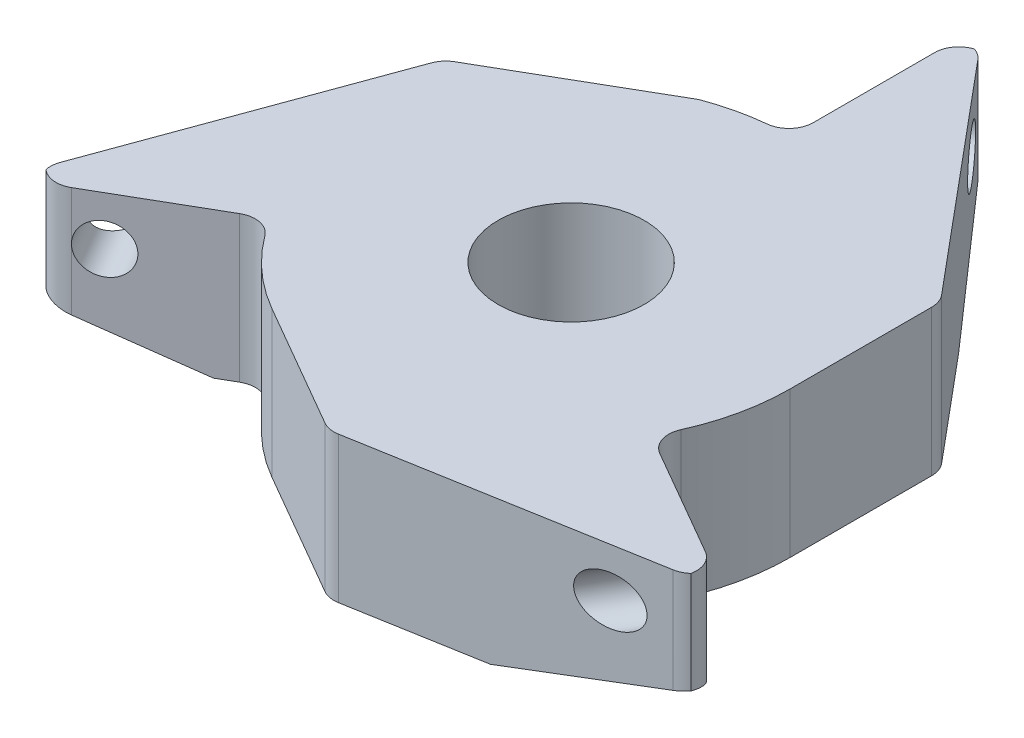
SolidWorks part; units mm, degrees
material "6061 Alloy"
ref_plane "Front Plane" through (0, 0, 0) normal (0, 0, 1) x (1, 0, 0)
ref_plane "Top Plane" through (0, 0, 0) normal (0, 1, 0) x (1, 0, 0)
ref_plane "Right Plane" through (0, 0, 0) normal (1, 0, 0) x (0, 0, -1)
sketch "Sketch1" plane through (0, 0, 0) normal (0, 1, 0) x (1, 0, 0)
  line L0 (0, 9.9499) -> (0, 14.9315)
  line L2 (1.141, 15.5732) -> (8.767, 6.4581)
  line L3 (9, 5.8165) -> (9, 0)
  line L4 (8.6168, -4.9749) -> (13.0497, -7.5342)
  line L6 (13.0349, -8.8432) -> (1.3281, -10.89)
  line L7 (0.6559, -10.771) -> (-4.5, -7.7942)
  line L8 (-8.5466, -5.0714) -> (-12.9311, -7.6027)
  line L10 (-14.0573, -6.9354) -> (-9.9764, 4.2264)
  line L11 (-9.5372, 4.749) -> (-3.1793, 8.4198)
  circle A0 centre (0, 0) radius 3
  arc A1 (-7.2419, -5.3437) -> (-4.5, -7.7942) centre (0, 0) ccw
  arc A2 (-0.9, 8.9549) -> (-3.1793, 8.4198) centre (0, 0) ccw
  arc A3 (8.2052, -3.698) -> (9, 0) centre (0, 0) ccw
  arc A4 (1.3281, -10.89) -> (0.6559, -10.771) centre (1.1559, -9.9049) cw
  arc A5 (13.5287, -8.6041) -> (13.0349, -8.8432) centre (12.8627, -7.8582) cw
  arc A6 (13.0497, -7.5342) -> (13.5287, -8.6041) centre (12.5497, -8.4003) cw
  arc A7 (8.2052, -3.698) -> (8.6168, -4.9749) centre (9.1168, -4.1089) ccw
  arc A8 (8.767, 6.4581) -> (9, 5.8165) centre (8, 5.8165) cw
  arc A9 (0.687, 15.8813) -> (1.141, 15.5732) centre (0.374, 14.9315) cw
  arc A10 (0, 14.9315) -> (0.687, 15.8813) centre (1, 14.9315) cw
  arc A11 (-7.2419, -5.3437) -> (-8.5466, -5.0714) centre (-8.0466, -5.9374) ccw
  arc A12 (-12.9311, -7.6027) -> (-14.0971, -7.4827) centre (-13.4311, -6.7367) cw
  arc A13 (-14.0573, -6.9354) -> (-14.0971, -7.4827) centre (-13.1181, -7.2788) ccw
  arc A14 (-9.5372, 4.749) -> (-9.9764, 4.2264) centre (-9.0372, 3.883) ccw
  arc A15 (0, 9.9499) -> (-0.9, 8.9549) centre (-1, 9.9499) cw
  point P22 (0.0395, -0.0685)
  point P43 (0, 9)
  dimension "D1" = 3
  dimension "D2" = 1
  dimension "D4" = 9
extrude "Boss-Extrude1" add sketch "Sketch1" along normal blind 6
sketch "Sketch2" plane through (0.0593, 0, 0.1027) normal (0.5, 0, 0.866) x (0.866, 0, -0.5)
  line L0 (-15, 6) -> (-9.9372, 6) construction
  line L2 (-16.3337, 1.9231) -> (-10.0569, -0.2316)
  line L3 (-10.0569, -0.2316) -> (-16.3337, -0.2316)
  line L4 (-16.3337, -0.2316) -> (-16.3337, 1.9231)
  circle A0 centre (-14, 4) radius 1
  dimension "D1" = 2
  dimension "D2" = 2
  dimension "D3" = 14
extrude "Cut-Extrude1" cut sketch "Sketch2" against normal through all
pattern_circular "CirPattern1" count 3 over 360 about axis through (0, 6, 0) along (0, 1, 0) of "Cut-Extrude1"
